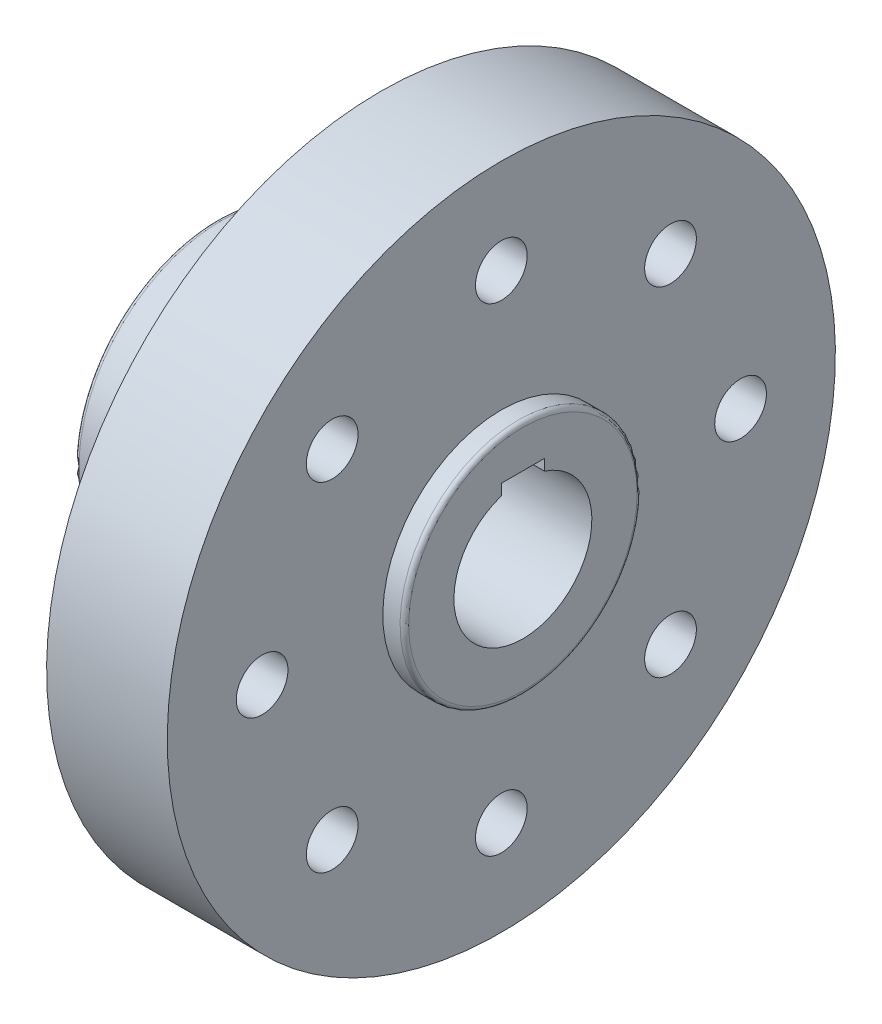
SolidWorks part; units mm, degrees
ref_plane "Front Plane" through (0, 0, 0) normal (0, 0, 1) x (1, 0, 0)
ref_plane "Top Plane" through (0, 0, 0) normal (0, 1, 0) x (1, 0, 0)
ref_plane "Right Plane" through (0, 0, 0) normal (1, 0, 0) x (0, 0, -1)
sketch "Sketch2" plane through (0, 0, 0) normal (0, 0, 1) x (1, 0, 0)
  line L0 (29.1143, 0) -> (-79.6704, 0) construction
  line L1 (29.1143, 0) -> (29.1143, 27.5)
  line L2 (29.1143, 27.5) -> (24.1143, 27.5)
  line L3 (24.1143, 27.5) -> (24.1143, 77.5)
  line L4 (24.1143, 77.5) -> (-3.8857, 77.5)
  line L5 (-3.8857, 77.5) -> (-3.8857, 74.5)
  line L6 (-3.8857, 74.5) -> (10.1143, 74.5)
  line L7 (10.1143, 74.5) -> (10.1143, 33)
  line L8 (10.1143, 33) -> (-41.8857, 33)
  line L9 (-41.8857, 33) -> (-41.8857, 0)
  line L10 (-41.8857, 0) -> (29.1143, 0)
  dimension "D1" = 77.5
  dimension "D2" = 33
  dimension "D3" = 27.5
  dimension "D4" = 28
  dimension "D5" = 5
  dimension "D6" = 14
  dimension "D7" = 38
  dimension "D8" = 71
  dimension "D9" = 3
revolve "Revolve1" add sketch "Sketch2" angle 360 about L0
sketch "Sketch3" plane through (29.1143, 0, 0) normal (1, 0, 0) x (0, 0, -1)
  line L0 (0, 0) -> (0, 81.1281) construction
  line L1 (0, 0) -> (0, -88.3947) construction
  line L3 (-5, 17.75) -> (5, 17.75)
  line L4 (-5, 17.75) -> (-5, 14.25)
  line L5 (-5, 14.25) -> (5, 14.25)
  line L6 (5, 17.75) -> (5, 14.25)
  line L7 (-5, 17.75) -> (5, 14.25) construction
  line L8 (-5, 14.25) -> (5, 17.75) construction
  circle A0 centre (0, 0) radius 16
  point P5 (0, 16)
  dimension "D1" = 32
  dimension "D2" = 17.75
  dimension "D3" = 10
extrude "Cut-Extrude2" cut sketch "Sketch3" against normal through all contours L4 A0 L6 L5 | L5 L6 L3 L4 region at (29.1143, -0.2825, 0)
sketch "Sketch4" plane through (24.1143, 0, 0) normal (1, 0, 0) x (0, 0, -1)
  line L0 (0, 77.5) -> (0, -77.5) construction
  circle A0 centre (0, 0) radius 77.5 construction
  circle A1 centre (0, 55.5) radius 6
  circle A2 centre (39.2444, 39.2444) radius 6
  circle A3 centre (55.5, 0) radius 6
  circle A4 centre (39.2444, -39.2444) radius 6
  circle A5 centre (0, -55.5) radius 6
  circle A6 centre (-39.2444, -39.2444) radius 6
  circle A7 centre (-55.5, 0) radius 6
  circle A8 centre (-39.2444, 39.2444) radius 6
  point P24 (0, 0)
  dimension "D1" = 12
  dimension "D2" = 55.5
  dimension "D3" = 8
extrude "Cut-Extrude3" cut sketch "Sketch4" against normal through all
fillet "Fillet1" radius 5 1 edges at (10.1143, 33, 0)
fillet "Fillet2" radius 2 1 edges at (10.1143, 74.5, 0)
fillet "Fillet3" radius 1 3 edges at (-3.8857, 74.5, 0) (29.1143, 27.5, 0) (-41.8857, 33, 0)
chamfer "Chamfer1" distance 2 angle 45 1 edges at (-41.8857, -16, 0)
